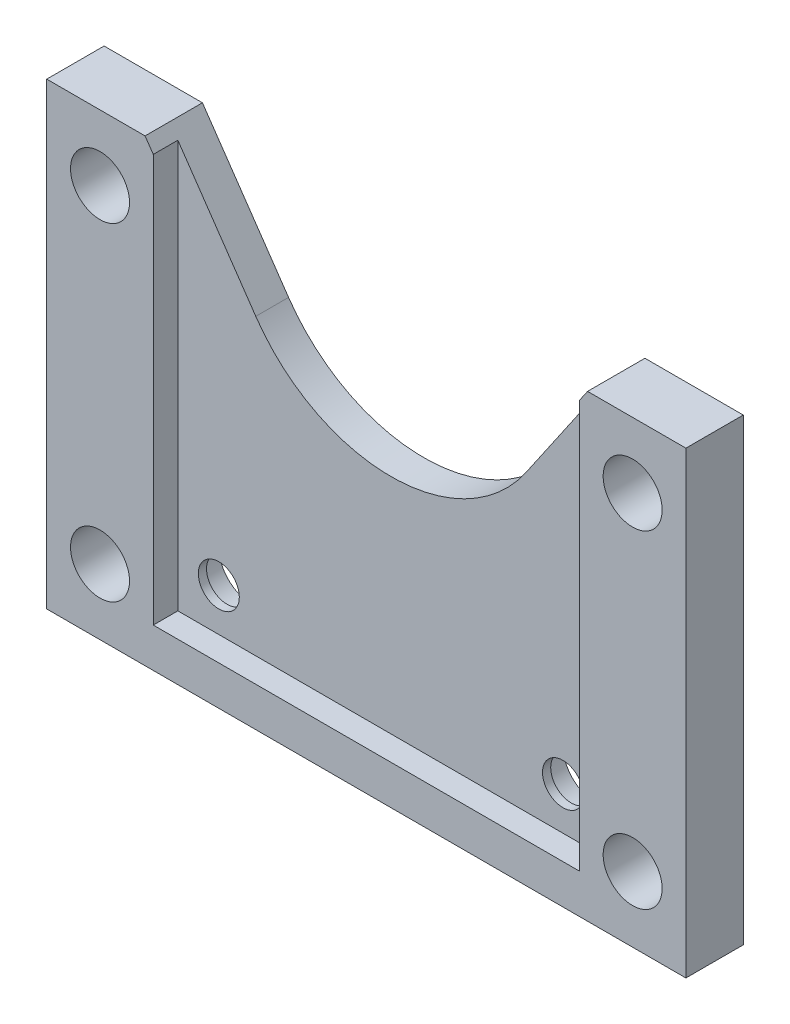
SolidWorks part; units mm, degrees
material "ABS"
ref_plane "正面" through (0, 0, 0) normal (0, 0, 1) x (1, 0, 0)
ref_plane "平面" through (0, 0, 0) normal (0, 1, 0) x (1, 0, 0)
ref_plane "右側面" through (0, 0, 0) normal (1, 0, 0) x (0, 0, -1)
sketch "ｽｹｯﾁ1" plane through (0, 0, 0) normal (0, 0, 1) x (1, 0, 0)
  line L0 (10.5, 0) -> (-10.5, 0) construction
  line L1 (0, 21) -> (0, -5) construction
  line L2 (19.5, -5) -> (-19.5, -5)
  line L3 (-19.5, -5) -> (-19.5, 23)
  line L4 (-19.5, 23) -> (-13.5, 23)
  line L5 (-13.5, 23) -> (-8.2456, 15.3422)
  line L6 (-16.25, -5) -> (-16.25, 23) construction
  line L7 (-13, -5) -> (-13, 22.2713) construction
  line L8 (19.5, -5) -> (19.5, 23)
  line L9 (19.5, 23) -> (13.5, 23)
  line L10 (13.5, 23) -> (8.2456, 15.3422)
  line L11 (-13, -2.6) -> (0, -2.6) construction
  circle A0 centre (-10.5, 0) radius 1.25
  circle A1 centre (10.5, 0) radius 1.25
  circle A2 centre (0, 21) radius 10 construction
  arc A3 (-8.2456, 15.3422) -> (8.2456, 15.3422) centre (0, 21) ccw
  circle A4 centre (-16.25, -1) radius 1.8
  circle A5 centre (-16.25, 19) radius 1.8
  circle A6 centre (16.25, -1) radius 1.8
  circle A7 centre (16.25, 19) radius 1.8
  point P4 (0, 0)
  dimension "D2" = 2.5
  dimension "D3" = 3.6
  dimension "D9" = 20
  dimension "D1" = 21
  dimension "D4" = 4
  dimension "D5" = 20
  dimension "D6" = 3.25
  dimension "D7" = 5
  dimension "D10" = 13
  dimension "D11" = 3.25
  dimension "D12" = 6
  dimension "D13" = 28
  dimension "D14" = 2.6
  dimension "D8" = 21
extrude "ﾎﾞｽ - 押し出し1" add sketch "ｽｹｯﾁ1" along normal blind 2
sketch "ｽｹｯﾁ3" plane through (0, 0, 2) normal (0, 0, 1) x (1, 0, 0)
  line L0 (-13, 22.2713) -> (-13, -2.6)
  line L1 (-13, -2.6) -> (13, -2.6)
  line L2 (19.5, -5) -> (-19.5, -5)
  line L3 (-19.5, -5) -> (-19.5, 23)
  line L4 (-19.5, 23) -> (-13.5, 23)
  line L5 (-13.5, 23) -> (-13, 22.2713)
  line L6 (0, -55) -> (0, 55) construction
  line L7 (13.5, 23) -> (13, 22.2713)
  line L8 (19.5, 23) -> (13.5, 23)
  line L9 (19.5, -5) -> (19.5, 23)
  line L10 (13, 22.2713) -> (13, -2.6)
  circle A0 centre (-16.25, 19) radius 1.8 construction
  circle A1 centre (-16.25, -1) radius 1.8 construction
  circle A2 centre (-16.25, 19) radius 1.8
  circle A3 centre (-16.25, -1) radius 1.8
  circle A4 centre (16.25, -1) radius 1.8
  circle A5 centre (16.25, 19) radius 1.8
  point P30 (0, -5)
  point P31 (0, -2.6)
extrude "ﾎﾞｽ - 押し出し2" add sketch "ｽｹｯﾁ3" along normal blind 1.5
sketch "ｽｹｯﾁ4" plane through (0, 0, 0) normal (0, 0, -1) x (-1, 0, 0)
  circle A0 centre (-10.5, 0) radius 2
  circle A1 centre (10.5, 0) radius 2
  dimension "D1" = 4
extrude "ｶｯﾄ - 押し出し1" cut sketch "ｽｹｯﾁ4" against normal blind 1.5
equation "\"D10@ｽｹｯﾁ1\"=26/2"
